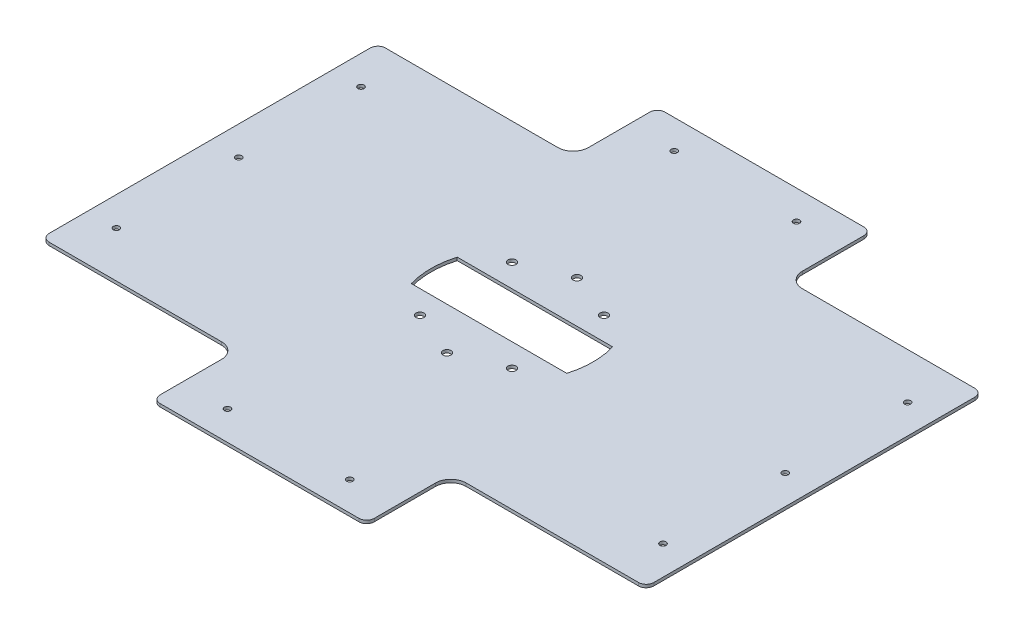
SolidWorks part; units mm, degrees
material "1060 Сплав"
ref_plane "Спереди" through (0, 0, 0) normal (0, 0, 1) x (1, 0, 0)
ref_plane "Сверху" through (0, 0, 0) normal (0, 1, 0) x (1, 0, 0)
ref_plane "Справа" through (0, 0, 0) normal (1, 0, 0) x (0, 0, -1)
sketch "Эскиз1" plane through (0, 0, 0) normal (0, 1, 0) x (1, 0, 0)
  line L1 (-65, -165.1043) -> (65, -165.1043)
  line L2 (-197.7687, -105) -> (-197.7687, 105)
  line L3 (-65, 165.1043) -> (65, 165.1043)
  line L4 (197.7687, -105) -> (197.7687, 105)
  line L18 (-284.5497, 0) -> (284.3305, 0) construction
  line L39 (-70, 120) -> (-70, 160.1043)
  line L40 (0, 262.7398) -> (0, -186.5795) construction
  line L41 (-192.7687, 110) -> (-80, 110)
  line L43 (-192.7687, -110) -> (-80, -110)
  line L44 (-70, -120) -> (-70, -160.1043)
  line L45 (70, 120) -> (70, 160.1043)
  line L46 (192.7687, 110) -> (80, 110)
  line L47 (192.7687, -110) -> (80, -110)
  line L48 (70, -120) -> (70, -160.1043)
  line L54 (160.9018, -110) -> (134.9018, -110)
  line L60 (160.9018, 110) -> (134.9018, 110)
  arc A0 (70, -120) -> (80, -110) centre (80, -120) cw
  arc A1 (70, 120) -> (80, 110) centre (80, 120) ccw
  arc A2 (-80, -110) -> (-70, -120) centre (-80, -120) cw
  arc A3 (-70, 120) -> (-80, 110) centre (-80, 120) cw
  arc A4 (192.7687, -110) -> (197.7687, -105) centre (192.7687, -105) ccw
  arc A5 (70, -160.1043) -> (65, -165.1043) centre (65, -160.1043) cw
  arc A6 (-70, -160.1043) -> (-65, -165.1043) centre (-65, -160.1043) ccw
  arc A7 (-192.7687, -110) -> (-197.7687, -105) centre (-192.7687, -105) cw
  arc A8 (-192.7687, 110) -> (-197.7687, 105) centre (-192.7687, 105) ccw
  arc A9 (197.7687, 105) -> (192.7687, 110) centre (192.7687, 105) ccw
  arc A10 (70, 160.1043) -> (65, 165.1043) centre (65, 160.1043) ccw
  arc A11 (-70, 160.1043) -> (-65, 165.1043) centre (-65, 160.1043) cw
  circle A22 centre (178.7687, 0) radius 2
  circle A23 centre (178.7687, 80) radius 2
  circle A24 centre (178.7687, -80) radius 2
  circle A25 centre (-178.7687, -80) radius 2
  circle A26 centre (-178.7687, 0) radius 2
  circle A27 centre (-178.7687, 80) radius 2
  circle A28 centre (40, 146.1043) radius 2
  circle A29 centre (-40, 146.1043) radius 2
  circle A30 centre (-40, -146.1043) radius 2
  circle A31 centre (40, -146.1043) radius 2
  point P0 (0, 0)
  point P3 (70, -110)
  point P8 (197.7687, 0)
  point P18 (-147.9018, 110)
  point P46 (70, 110)
  point P52 (-70, -110)
  point P55 (-70, 110)
  point P56 (-147.9018, 0)
  point P77 (197.7687, -110)
  point P80 (70, -165.1043)
  point P83 (-70, -165.1043)
  point P86 (-197.7687, -110)
  point P89 (-197.7687, 110)
  point P92 (197.7687, 110)
  point P95 (70, 165.1043)
  point P98 (-70, 165.1043)
  dimension "D2" = 4
  dimension "D6" = 10
  dimension "D11" = 40
  dimension "D12" = 330.2086
  dimension "D4" = 5
  dimension "D1" = 4
  dimension "D8" = 4
  dimension "D3" = 19
  dimension "D5" = 80
  dimension "D7" = 19
  dimension "D9" = 140
  dimension "D10" = 19
  dimension "D13" = 395.5373
sketch "Эскиз2" plane through (0, 0, 0) normal (0, 1, 0) x (1, 0, 0)
  line L0 (-162.9105, 114) -> (-136.9105, 114)
  line L1 (-162.9105, 114) -> (-162.9105, 0)
  line L2 (-162.9105, 0) -> (-136.9105, 0)
  line L3 (-136.9105, 114) -> (-136.9105, 0)
  line L4 (-149.9105, -192.6295) -> (-149.9105, 209.9923) construction
  line L5 (-162.9105, 0) -> (-136.9105, 0)
  line L6 (-162.9105, 0) -> (-162.9105, -114)
  line L7 (-162.9105, -114) -> (-136.9105, -114)
  line L8 (-136.9105, 0) -> (-136.9105, -114)
  line L9 (-99.9105, -123.5568) -> (-199.9105, -123.5568)
  line L10 (-99.9105, 163.4996) -> (-199.9105, 163.4996)
  line L11 (-99.9105, 163.4996) -> (-99.9105, 123.4996)
  line L12 (-99.9105, 123.4996) -> (-199.9105, 123.4996)
  line L13 (-199.9105, 163.4996) -> (-199.9105, 123.4996)
  line L14 (-199.9105, -163.5568) -> (-199.9105, -123.5568)
  line L15 (-99.9105, -163.5568) -> (-199.9105, -163.5568)
  line L16 (-99.9105, -163.5568) -> (-99.9105, -123.5568)
  line L17 (-284.5497, 0) -> (284.3305, 0) construction
  point P11 (-149.9105, 0)
  point P12 (-149.9105, 0)
sketch "Эскиз3" plane through (0, 0, 0) normal (0, 1, 0) x (1, 0, 0)
  line L0 (-89.8176, -177.9027) -> (70.2405, -177.9027)
  line L1 (-209.7886, -106.9112) -> (-209.7886, 106.8353)
  line L2 (-80.029, 172.0973) -> (50.2405, 172.0973)
  line L3 (170.2114, -106.9112) -> (170.2114, 103.9123)
  line L4 (-87.1938, 124.0033) -> (-87.1938, 164.9326)
  line L5 (-202.6239, 114) -> (-97.1971, 114)
  line L6 (-202.6239, -114.076) -> (-106.9857, -114.076)
  line L7 (-96.9823, -124.0793) -> (-96.9823, -170.738)
  line L8 (57.4052, 121.0803) -> (57.4052, 164.9326)
  line L9 (163.0467, 111.077) -> (67.4085, 111.077)
  line L10 (163.0467, -114.076) -> (87.4085, -114.076)
  line L11 (77.4052, -124.0793) -> (77.4052, -170.738)
  line L13 (-162.9105, 114) -> (-136.9105, 114) construction
  arc A0 (77.4052, -124.0793) -> (87.4085, -114.076) centre (87.4085, -124.0793) cw
  arc A1 (57.4052, 121.0803) -> (67.4085, 111.077) centre (67.4085, 121.0803) ccw
  arc A2 (-106.9857, -114.076) -> (-96.9823, -124.0793) centre (-106.9857, -124.0793) cw
  arc A3 (-87.1938, 124.0033) -> (-97.1971, 114) centre (-97.1971, 124.0033) cw
  arc A4 (-80.029, 172.0973) -> (-87.1938, 164.9326) centre (-80.029, 164.9326) ccw
  arc A5 (50.2405, 172.0973) -> (57.4052, 164.9326) centre (50.2405, 164.9326) cw
  arc A6 (170.2114, 103.9123) -> (163.0467, 111.077) centre (163.0467, 103.9123) ccw
  arc A7 (170.2114, -106.9112) -> (163.0467, -114.076) centre (163.0467, -106.9112) cw
  arc A8 (70.2405, -177.9027) -> (77.4052, -170.738) centre (70.2405, -170.738) ccw
  arc A9 (-89.8176, -177.9027) -> (-96.9823, -170.738) centre (-89.8176, -170.738) cw
  arc A10 (-209.7886, -106.9112) -> (-202.6239, -114.076) centre (-202.6239, -106.9112) ccw
  arc A11 (-209.7886, 106.8353) -> (-202.6239, 114) centre (-202.6239, 106.8353) cw
  point P36 (115.2276, 111.077)
  point P39 (-149.9105, 114)
  point P42 (-149.9105, 114)
  dimension "D3" = 10.0033
  dimension "D4" = 7.1647
  dimension "D1" = 380
  dimension "D2" = 350
  dimension "D5" = 112.8062
  dimension "D6" = 63.8267
  dimension "D7" = 61.0203
extrude "Бобышка-Вытянуть1" add sketch "Эскиз1" along normal blind 2 separate body contours A11 L39 A3 L41 L43 A2 L44 A6 L1 A5 L48 A0 L47 L46 A1 L45 A10 L3 | L4 A9 L46 L47 A4 | L46 | L47 | L41 A8 L2 A7 L43 region at (0, 0, 0)
sketch "Эскиз4" plane through (0, 2, 0) normal (0, 1, 0) x (1, 0, 0)
  line L0 (197.7687, 0) -> (-197.7687, 0) construction
  line L1 (197.7687, -105) -> (197.7687, 105) construction
  line L2 (-197.7687, -105) -> (-197.7687, 105) construction
  line L3 (197.7687, 0) -> (10, 0) construction
  line L4 (-22, 0) -> (0, 0) construction
  line L5 (0, 0) -> (0, 42.54) construction
  circle A1 centre (0, 42.54) radius 2.6
  circle A2 centre (0, -42.54) radius 2.6
  circle A7 centre (0, 0) radius 42.54 construction
  circle A8 centre (30.0803, 30.0803) radius 2.6
  circle A9 centre (-30.0803, -30.0803) radius 2.6
  circle A10 centre (-30.0803, 30.0803) radius 2.6
  circle A11 centre (30.0803, -30.0803) radius 2.6
  point P14 (0, 0)
  point P21 (0, 0)
  point P26 (0, 0)
  point P29 (0, 0)
  dimension "D1" = 2
  dimension "D2" = 5.2
  dimension "D3" = 2
  dimension "D4" = 2
extrude "Вырез-Вытянуть1" cut sketch "Эскиз4" against normal through all
sketch "Эскиз5" plane through (0, 0, 0) normal (0, -1, 0) x (1, 0, 0)
  line L0 (50.8331, -15) -> (-50.8331, -15)
  line L7 (50.8331, 15) -> (-50.8331, 15)
  arc A0 (50.8331, -15) -> (50.8331, 15) centre (0, 0) ccw
  arc A1 (-50.8331, 15) -> (-50.8331, -15) centre (0, 0) ccw
  point P0 (0, 0)
  dimension "D2" = 101.6661
  dimension "D3" = 101.6661
  dimension "D1" = 30
extrude "Вырез-Вытянуть2" cut sketch "Эскиз5" against normal through all
